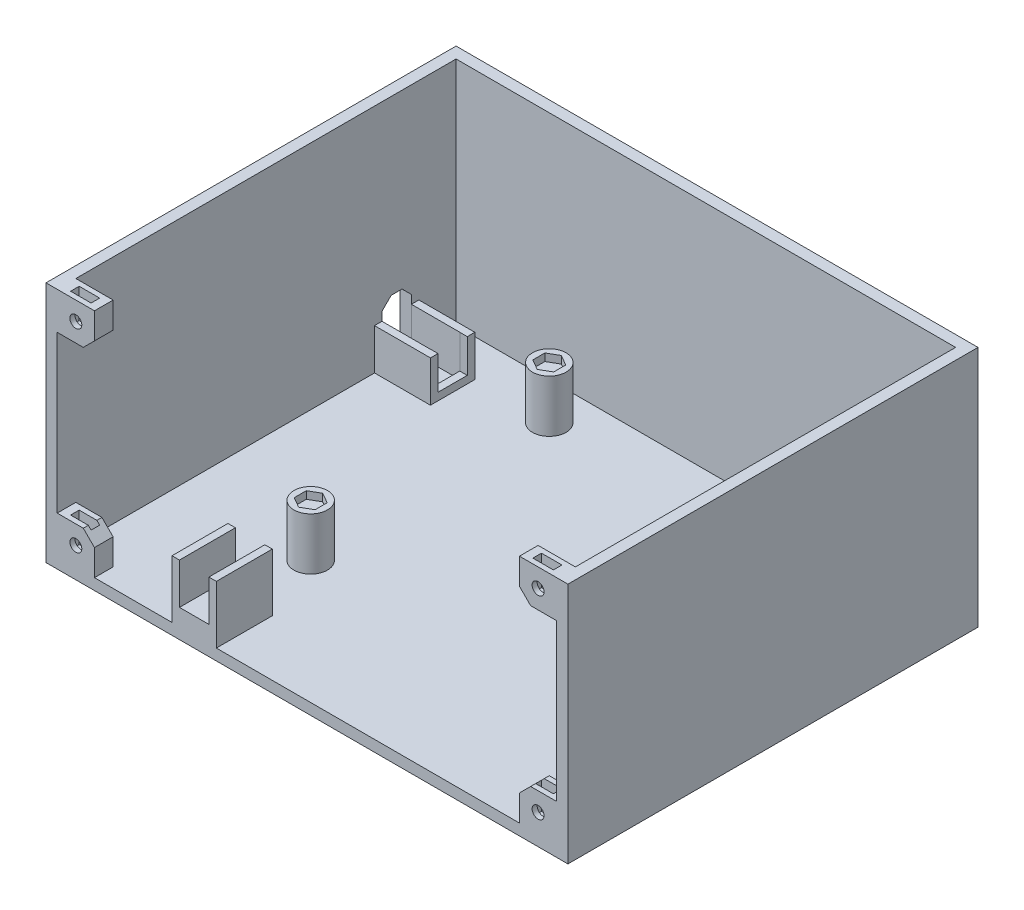
SolidWorks part; units mm, degrees
ref_plane "Спереди" through (0, 0, 0) normal (0, 0, 1) x (1, 0, 0)
ref_plane "Сверху" through (0, 0, 0) normal (0, 1, 0) x (1, 0, 0)
ref_plane "Справа" through (0, 0, 0) normal (1, 0, 0) x (0, 0, -1)
sketch "Эскиз2" plane through (0, 0, 0) normal (0, 0, 1) x (1, 0, 0)
  line L1 (-70, 32.5) -> (70, 32.5)
  line L2 (-70, 32.5) -> (-70, -32.5)
  line L3 (-70, -32.5) -> (70, -32.5)
  line L4 (70, 32.5) -> (70, -32.5)
  line L5 (-70, 32.5) -> (70, -32.5) construction
  line L6 (-70, -32.5) -> (70, 32.5) construction
  point P0 (0, 0)
  dimension "D1" = 65
  dimension "D2" = 140
extrude "Бобышка-Вытянуть1" add sketch "Эскиз2" along normal blind 110
sketch "Эскиз3" plane through (0, 32.5, 0) normal (0, 1, 0) x (1, 0, 0)
  line L0 (-70, -110) -> (-70, 0) construction
  line L1 (-67, -3) -> (67, -3)
  line L2 (-67, -3) -> (-67, -110)
  line L3 (-67, -110) -> (67, -110)
  line L4 (67, -3) -> (67, -110)
  line L5 (-67, -3) -> (67, -110) construction
  line L6 (-67, -110) -> (67, -3) construction
  line L8 (70, 0) -> (-70, 0) construction
  point P0 (0, -56.5)
  dimension "D1" = 107
  dimension "D2" = 134
  dimension "D3" = 3
  dimension "D4" = 3
extrude "Вырез-Вытянуть1" cut sketch "Эскиз3" against normal blind 62
sketch "Эскиз4" plane through (0, 0, 110) normal (0, 0, 1) x (1, 0, 0)
  line L0 (57, -19.5) -> (57, -29.5)
  line L1 (-67, -19.5) -> (-57, -19.5)
  line L2 (-67, -19.5) -> (-67, -29.5)
  line L3 (-67, -29.5) -> (-57, -29.5)
  line L4 (-57, -19.5) -> (-57, -29.5)
  line L5 (-67, -19.5) -> (-57, -29.5) construction
  line L6 (-67, -29.5) -> (-57, -19.5) construction
  line L7 (57, -19.5) -> (67, -19.5)
  line L8 (67, -19.5) -> (67, -29.5)
  line L9 (57, -29.5) -> (67, -29.5)
  line L10 (67, -29.5) -> (67, 32.5) construction
  circle A0 centre (-62, -24.5) radius 1.6
  circle A1 centre (62, -24.5) radius 1.6
  point P0 (-62, -24.5)
  point P11 (57, -24.5)
  point P13 (-57, -24.5)
  dimension "D2" = 3.2
  dimension "D1" = 10
  dimension "D3" = 2
extrude "Бобышка-Вытянуть2" add sketch "Эскиз4" against normal blind 5
sketch "Эскиз5" plane through (0, 0, 110) normal (0, 0, 1) x (1, 0, 0)
  line L0 (57, 32.5) -> (57, 22.5)
  line L1 (-67, 32.5) -> (-57, 32.5)
  line L2 (-67, 32.5) -> (-67, 22.5)
  line L3 (-67, 22.5) -> (-57, 22.5)
  line L4 (-57, 32.5) -> (-57, 22.5)
  line L5 (-67, 32.5) -> (-57, 22.5) construction
  line L6 (-67, 22.5) -> (-57, 32.5) construction
  line L7 (57, 32.5) -> (67, 32.5)
  line L8 (67, 32.5) -> (67, 22.5)
  line L9 (57, 22.5) -> (67, 22.5)
  line L11 (67, -29.5) -> (67, 32.5) construction
  circle A0 centre (-62, 27.5) radius 1.6
  circle A1 centre (62, 27.5) radius 1.6
  point P0 (-62, 27.5)
  dimension "D4" = 3.2
  dimension "D1" = 10
  dimension "D2" = 10
  dimension "D3" = 2
extrude "Бобышка-Вытянуть3" add sketch "Эскиз5" against normal blind 5
sketch "Эскиз6" plane through (0, 32.5, 0) normal (0, 1, 0) x (1, 0, 0)
  line L0 (-57, -105) -> (-57, -110) construction
  line L1 (-64.75, -106.35) -> (-59.25, -106.35)
  line L2 (-64.75, -106.35) -> (-64.75, -108.65)
  line L3 (-64.75, -108.65) -> (-59.25, -108.65)
  line L4 (-59.25, -106.35) -> (-59.25, -108.65)
  line L5 (-64.75, -106.35) -> (-59.25, -108.65) construction
  line L6 (-64.75, -108.65) -> (-59.25, -106.35) construction
  line L7 (59.25, -106.35) -> (59.25, -108.65)
  line L8 (59.25, -106.35) -> (64.75, -106.35)
  line L9 (64.75, -106.35) -> (64.75, -108.65)
  line L10 (59.25, -108.65) -> (64.75, -108.65)
  point P0 (-62, -107.5)
  dimension "D1" = 2.3
  dimension "D2" = 5.5
  dimension "D3" = 5
  dimension "D4" = 2.5
  dimension "D6" = 1.35
  dimension "D7" = 2.25
  dimension "D8" = 2.25
  dimension "D9" = 1.35
  dimension "D5" = 2
extrude "Вырез-Вытянуть2" cut sketch "Эскиз6" against normal blind 8
sketch "Эскиз8" plane through (0, -19.5, 0) normal (0, 1, 0) x (1, 0, 0)
  line L0 (59.25, -106.35) -> (59.25, -108.65)
  line L1 (-64.75, -106.35) -> (-59.25, -106.35)
  line L2 (-64.75, -106.35) -> (-64.75, -108.65)
  line L3 (-64.75, -108.65) -> (-59.25, -108.65)
  line L4 (-59.25, -106.35) -> (-59.25, -108.65)
  line L5 (-64.75, -106.35) -> (-59.25, -108.65) construction
  line L6 (-64.75, -108.65) -> (-59.25, -106.35) construction
  line L7 (59.25, -106.35) -> (64.75, -106.35)
  line L8 (64.75, -106.35) -> (64.75, -108.65)
  line L9 (59.25, -108.65) -> (64.75, -108.65)
  line L10 (67, -105) -> (57, -105) construction
  line L11 (57, -105) -> (57, -110) construction
  point P0 (-62, -107.5)
  dimension "D1" = 2.3
  dimension "D2" = 5.5
  dimension "D3" = 2.5
  dimension "D4" = 5
  dimension "D5" = 1.35
  dimension "D6" = 2.25
extrude "Вырез-Вытянуть3" cut sketch "Эскиз8" against normal blind 8
chamfer "Фаска1" distance 3 angle 45 4 edges at (57, 22.5, 107.5) (57, -19.5, 107.5) (-57, 22.5, 107.5) (-57, -19.5, 107.5)
sketch "Эскиз9" plane through (0, -29.5, 0) normal (0, 1, 0) x (1, 0, 0)
  line L0 (67, -3) -> (-67, -3) construction
  line L1 (67, -105) -> (67, -3) construction
  circle A0 centre (54, -13) radius 4.5
  circle A1 centre (-32, -13) radius 4.5
  circle A2 centre (-32, -77) radius 4.5
  circle A3 centre (54, -77) radius 4.5
  point P2 (50.5445, -13.1853)
  point P3 (0, 0)
  dimension "D1" = 9
  dimension "D4" = 10
  dimension "D5" = 13
  dimension "D2" = 2
  dimension "D3" = 2
extrude "Бобышка-Вытянуть4" add sketch "Эскиз9" along normal blind 14
sketch "Эскиз12" plane through (0, -15.5, 0) normal (0, 1, 0) x (1, 0, 0)
  line L0 (54, -9.7668) -> (51.2, -11.3834)
  line L1 (-32, -9.7668) -> (-34.8, -11.3834)
  line L2 (-34.8, -11.3834) -> (-34.8, -14.6166)
  line L3 (-34.8, -14.6166) -> (-32, -16.2332)
  line L4 (-32, -16.2332) -> (-29.2, -14.6166)
  line L5 (-29.2, -14.6166) -> (-29.2, -11.3834)
  line L6 (-29.2, -11.3834) -> (-32, -9.7668)
  line L7 (51.2, -11.3834) -> (51.2, -14.6166)
  line L8 (51.2, -14.6166) -> (54, -16.2332)
  line L9 (54, -16.2332) -> (56.8, -14.6166)
  line L10 (56.8, -14.6166) -> (56.8, -11.3834)
  line L11 (56.8, -11.3834) -> (54, -9.7668)
  line L12 (54, -73.7668) -> (51.2, -75.3834)
  line L13 (51.2, -75.3834) -> (51.2, -78.6166)
  line L14 (51.2, -78.6166) -> (54, -80.2332)
  line L15 (54, -80.2332) -> (56.8, -78.6166)
  line L16 (56.8, -78.6166) -> (56.8, -75.3834)
  line L17 (56.8, -75.3834) -> (54, -73.7668)
  line L18 (-32, -73.7668) -> (-34.8, -75.3834)
  line L19 (-34.8, -75.3834) -> (-34.8, -78.6166)
  line L20 (-34.8, -78.6166) -> (-32, -80.2332)
  line L21 (-32, -80.2332) -> (-29.2, -78.6166)
  line L22 (-29.2, -78.6166) -> (-29.2, -75.3834)
  line L23 (-29.2, -75.3834) -> (-32, -73.7668)
  circle A0 centre (-32, -13) radius 3.2332 construction
  dimension "D1" = 2
  dimension "D2" = 2
extrude "Вырез-Вытянуть4" cut sketch "Эскиз12" against normal blind 2
sketch "Эскиз13" plane through (-70, 0, 0) normal (-1, 0, 0) x (0, 0, 1)
  line L0 (15, -29.3) -> (22.9, -29.3)
  line L1 (22.9, -29.3) -> (22.9, -16.2)
  line L2 (22.9, -16.2) -> (20.4058, -13.7)
  line L3 (20.4058, -13.7) -> (17.4942, -13.7)
  line L4 (17.4942, -13.7) -> (15, -16.2)
  line L5 (15, -16.2) -> (15, -29.3)
  line L6 (0, 32.5) -> (0, -32.5) construction
  line L7 (110, -32.5) -> (0, -32.5) construction
  point P6 (18.95, -13.7)
  point P7 (18.95, -29.3)
  dimension "D1" = 7.9
  dimension "D2" = 15.6
  dimension "D3" = 2.5
  dimension "D4" = 15
  dimension "D5" = 3.2
extrude "Вырез-Вытянуть5" cut sketch "Эскиз13" against normal up to next
sketch "Эскиз15" plane through (0, -29.5, 0) normal (0, 1, 0) x (1, 0, 0)
  line L0 (-67, -24.8782) -> (-52, -24.8782)
  line L1 (-52, -24.8782) -> (-52, -12.9782)
  line L2 (-52, -12.9782) -> (-67, -12.9782)
  line L3 (-67, -12.9782) -> (-67, -14.9782)
  line L4 (-67, -14.9782) -> (-54, -14.9782)
  line L5 (-54, -14.9782) -> (-54, -22.8782)
  line L6 (-54, -22.8782) -> (-67, -22.8782)
  line L7 (-67, -24.8782) -> (-67, -22.8782)
  line L9 (-67, -3) -> (-67, -105) construction
  line L11 (67, -3) -> (-67, -3) construction
  dimension "D1" = 7.9
  dimension "D2" = 2
  dimension "D3" = 2
  dimension "D4" = 2
  dimension "D5" = 15
  dimension "D6" = 9.9782
extrude "Бобышка-Вытянуть5" add sketch "Эскиз15" along normal blind 11
sketch "Эскиз16" plane through (0, -18.5, 0) normal (0, 1, 0) x (1, 0, 0)
  line L0 (-52, -24.8782) -> (-52, -12.9782) construction
  line L2 (-54.9087, -14.9995) -> (-49.0913, -14.9995)
  line L3 (-54.9087, -14.9995) -> (-54.9087, -22.8569)
  line L4 (-54.9087, -22.8569) -> (-49.0913, -22.8569)
  line L5 (-49.0913, -14.9995) -> (-49.0913, -22.8569)
  line L6 (-54.9087, -14.9995) -> (-49.0913, -22.8569) construction
  line L7 (-54.9087, -22.8569) -> (-49.0913, -14.9995) construction
  point P3 (-52, -18.9282)
  dimension "D1" = 7.8574
  dimension "D2" = 5.8174
extrude "Вырез-Вытянуть6" cut sketch "Эскиз16" against normal blind 9
sketch "Эскиз17" plane through (0, -29.5, 0) normal (0, 1, 0) x (1, 0, 0)
  line L0 (-36.2, -110) -> (-36.2, -95)
  line L1 (-36.2, -95) -> (-24.3, -95)
  line L2 (-24.3, -95) -> (-24.3, -110)
  line L3 (-24.3, -110) -> (-26.3, -110)
  line L4 (-26.3, -110) -> (-26.3, -97)
  line L5 (-26.3, -97) -> (-34.2, -97)
  line L6 (-34.2, -97) -> (-34.2, -110)
  line L7 (-34.2, -110) -> (-36.2, -110)
  line L8 (-70, -110) -> (-70, 0) construction
  line L9 (-57, -110) -> (57, -110) construction
  point P7 (-26.3, -103.5)
  dimension "D1" = 2
  dimension "D2" = 2
  dimension "D3" = 2
  dimension "D4" = 15
  dimension "D5" = 33.8
  dimension "D6" = 7.9
extrude "Бобышка-Вытянуть6" add sketch "Эскиз17" along normal blind 15.5
sketch "Эскиз18" plane through (0, -14, 0) normal (0, 1, 0) x (1, 0, 0)
  line L1 (-34.2, -89.315) -> (-26.3, -89.315)
  line L2 (-34.2, -89.315) -> (-34.2, -100.685)
  line L3 (-34.2, -100.685) -> (-26.3, -100.685)
  line L4 (-26.3, -89.315) -> (-26.3, -100.685)
  line L5 (-34.2, -89.315) -> (-26.3, -100.685) construction
  line L6 (-34.2, -100.685) -> (-26.3, -89.315) construction
  line L8 (-24.3, -95) -> (-36.2, -95) construction
  line L9 (-26.3, -97) -> (-26.3, -110) construction
  point P0 (-30.25, -95)
  dimension "D1" = 11.37
  dimension "D2" = 7.9
extrude "Вырез-Вытянуть7" cut sketch "Эскиз18" against normal blind 9.5
sketch "Эскиз19" plane through (0, -29.5, 0) normal (0, 1, 0) x (1, 0, 0)
  line L1 (-34.2, -97) -> (-26.3, -97)
  line L2 (-34.2, -97) -> (-34.2, -110)
  line L3 (-34.2, -110) -> (-26.3, -110)
  line L4 (-26.3, -97) -> (-26.3, -110)
  line L6 (-26.3, -95) -> (-26.3, -110) construction
  line L7 (-26.3, -97) -> (-26.3, -110) construction
  dimension "D1" = 13
  dimension "D2" = 7.9
extrude "Бобышка-Вытянуть7" add sketch "Эскиз19" along normal blind 4.5
